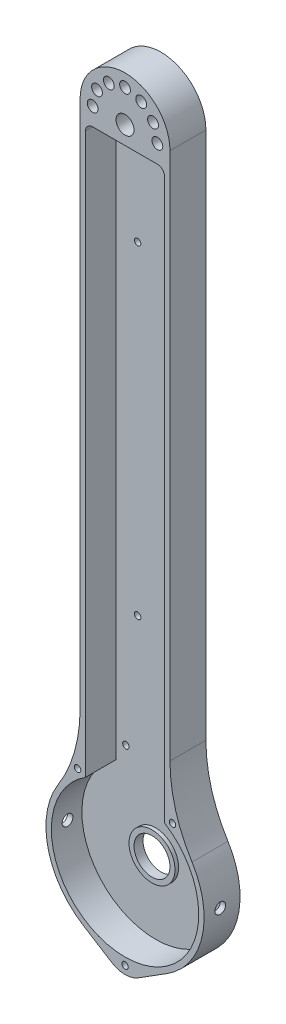
SolidWorks part; units mm, degrees
ref_plane "Front Plane" through (0, 0, 0) normal (0, 0, 1) x (1, 0, 0)
ref_plane "Top Plane" through (0, 0, 0) normal (0, 1, 0) x (1, 0, 0)
ref_plane "Right Plane" through (0, 0, 0) normal (1, 0, 0) x (0, 0, -1)
sketch "Sketch1" plane through (0, 0, 0) normal (0, 0, 1) x (1, 0, 0)
  line L0 (0, 0) -> (0, 228.6) construction
  line L1 (-15.875, 228.6) -> (-15.875, 41.8859)
  line L2 (15.875, 228.6) -> (15.875, 41.8859)
  line L3 (0, 19.2033) -> (0, -85.9778) construction
  line L4 (-40.6019, -33.02) -> (61.4714, -33.02) construction
  line L5 (-4.7378, -30.0359) -> (-14.8903, -23.6415)
  line L6 (4.7378, -30.0359) -> (14.8903, -23.6415)
  arc A0 (15.875, 228.6) -> (-15.875, 228.6) centre (0, 228.6) ccw
  circle A4 centre (0, 0) radius 6.35
  circle A5 centre (0, 228.6) radius 3.175
  arc A6 (-23.6589, 14.8628) -> (-14.8903, -23.6415) centre (0, 0) ccw
  arc A7 (23.6589, 14.8628) -> (15.875, 41.8859) centre (66.675, 41.8859) cw
  arc A8 (-15.875, 41.8859) -> (-23.6589, 14.8628) centre (-66.675, 41.8859) cw
  arc A9 (4.7378, -30.0359) -> (-4.7378, -30.0359) centre (0, -22.5136) cw
  arc A10 (14.8903, -23.6415) -> (23.6589, 14.8628) centre (0, 0) ccw
  point P17 (0, -33.02)
  point P19 (0, -33.02)
  dimension "D2" = 31.75
  dimension "D3" = 33.02
  dimension "D4" = 50.8
  dimension "D5" = 27.94
  dimension "D6" = 8.89
  dimension "D1" = 228.6
extrude "Boss-Extrude1" add sketch "Sketch1" along normal blind 12.7
sketch3d "3DSketch1" plane through (0, 0, 0) normal (0, 0, 1) x (1, 0, 0)
  dimension "D1" = 15.875
sketch3d "3DSketch2"
  line L0 (0, 0, 0) -> (0, 0, 6.985) construction
  circle A0 centre (0, 0, 6.985) radius 1.905
  point P4 (1.905, 0, 6.985)
sketch "Sketch2" plane through (0, 0, 12.7) normal (0, 0, 1) x (1, 0, 0)
  line L0 (-11.43, 222.25) -> (11.43, 222.25)
  line L1 (-13.97, 219.71) -> (-13.97, 21.9695)
  line L2 (13.97, 219.71) -> (13.97, 21.9695)
  circle A0 centre (0, 228.6) radius 3.175 construction
  arc A1 (-13.97, 21.9695) -> (13.97, 21.9695) centre (0, 0) ccw
  circle A2 centre (0, 228.6) radius 3.175 construction
  arc A3 (-11.43, 222.25) -> (-13.97, 219.71) centre (-11.43, 219.71) ccw
  arc A4 (13.97, 219.71) -> (11.43, 222.25) centre (11.43, 219.71) ccw
  point P12 (-13.97, 222.25)
  point P15 (13.97, 222.25)
  dimension "D2" = 27.94
  dimension "D4" = 2.54
  dimension "D5" = 2.54
  dimension "D1" = 6.35
  dimension "D3" = 13.97
extrude "Cut-Extrude1" cut sketch "Sketch2" against normal blind 10.795
extrude "Cut-Extrude2" cut sketch "3DSketch2" along direction (-1, 0, 0) on the side against the normal through all and the other way through all
sketch "Sketch3" plane through (0, 0, 1.905) normal (0, 0, 1) x (1, 0, 0)
  circle A0 centre (0, 0) radius 8.128
  circle A1 centre (0, 0) radius 6.35
extrude "Boss-Extrude2" add sketch "Sketch3" along normal blind 1.27
sketch "Sketch4" plane through (0, 0, 12.7) normal (0, 0, 1) x (1, 0, 0)
  line L0 (0, 228.6) -> (0, -81.1037) construction
  line L1 (-22.8257, 219.71) -> (25.3321, 219.71) construction
  circle A0 centre (0, 219.71) radius 1.5875
  circle A1 centre (-6.35, 184.15) radius 1.143
  circle A2 centre (6.35, 184.15) radius 1.143
  circle A3 centre (-6.35, 69.85) radius 1.143
  circle A4 centre (6.35, 69.85) radius 1.143
  circle A5 centre (-16.764, 23.241) radius 1.143
  circle A6 centre (16.764, 23.241) radius 1.143
  circle A7 centre (0, -28.575) radius 1.143
  circle A8 centre (-10.4775, 28.1178) radius 1.143
  circle A9 centre (10.4775, 28.1178) radius 1.143
  dimension "D2" = 6.35
  dimension "D6" = 10.4775
  dimension "D1" = 8.89
  dimension "D3" = 6.35
  dimension "D4" = 6.35
  dimension "D5" = 6.35
  dimension "D7" = 10.4775
  dimension "D8" = 16.764
  dimension "D9" = 16.764
  dimension "D10" = 44.45
  dimension "D11" = 44.45
  dimension "D12" = 158.75
  dimension "D13" = 158.75
  dimension "D14" = 200.4822
  dimension "D15" = 200.4822
  dimension "D16" = 205.359
  dimension "D17" = 205.359
  dimension "D18" = 257.175
extrude "Cut-Extrude3" cut sketch "Sketch4" against normal blind 31.75
sketch "Sketch5" plane through (0, 0, 12.7) normal (0, 0, 1) x (1, 0, 0)
  line L0 (0, 228.6) -> (-31.5289, 228.6) construction
  circle A0 centre (0, 228.6) radius 11.43 construction
  circle A1 centre (-11.43, 228.6) radius 1.905
  circle A2 centre (-9.8987, 234.315) radius 1.905
  circle A3 centre (-5.715, 238.4987) radius 1.905
  circle A4 centre (0, 240.03) radius 1.905
  circle A5 centre (5.715, 238.4987) radius 1.905
  circle A6 centre (9.8987, 234.315) radius 1.905
  circle A7 centre (11.43, 228.6) radius 1.905
  point P20 (0, 228.6)
  dimension "D1" = 7
extrude "Cut-Extrude4" cut sketch "Sketch5" against normal blind 7.62
sketch "Sketch6" plane through (0, 0, 0) normal (0, 0, -1) x (-1, 0, 0)
  line L1 (-1.5875, 227.0638) -> (1.5875, 227.0638)
  line L2 (-1.5875, 227.0638) -> (-1.5875, 219.71)
  line L3 (-1.5875, 219.71) -> (1.5875, 219.71)
  line L4 (1.5875, 227.0638) -> (1.5875, 219.71)
  circle A0 centre (0, 219.71) radius 1.5875 construction
  dimension "D1" = 3.175
  dimension "D2" = 1.5875
  dimension "D3" = 0
extrude "Cut-Extrude5" cut sketch "Sketch6" against normal blind 1.016
sketch "Sketch7" plane through (0, 0, 0) normal (0, 0, -1) x (-1, 0, 0)
  circle A0 centre (0, 228.6) radius 4.445
  dimension "D1" = 8.89
extrude "Cut-Extrude6" cut sketch "Sketch7" against normal blind 1.27
